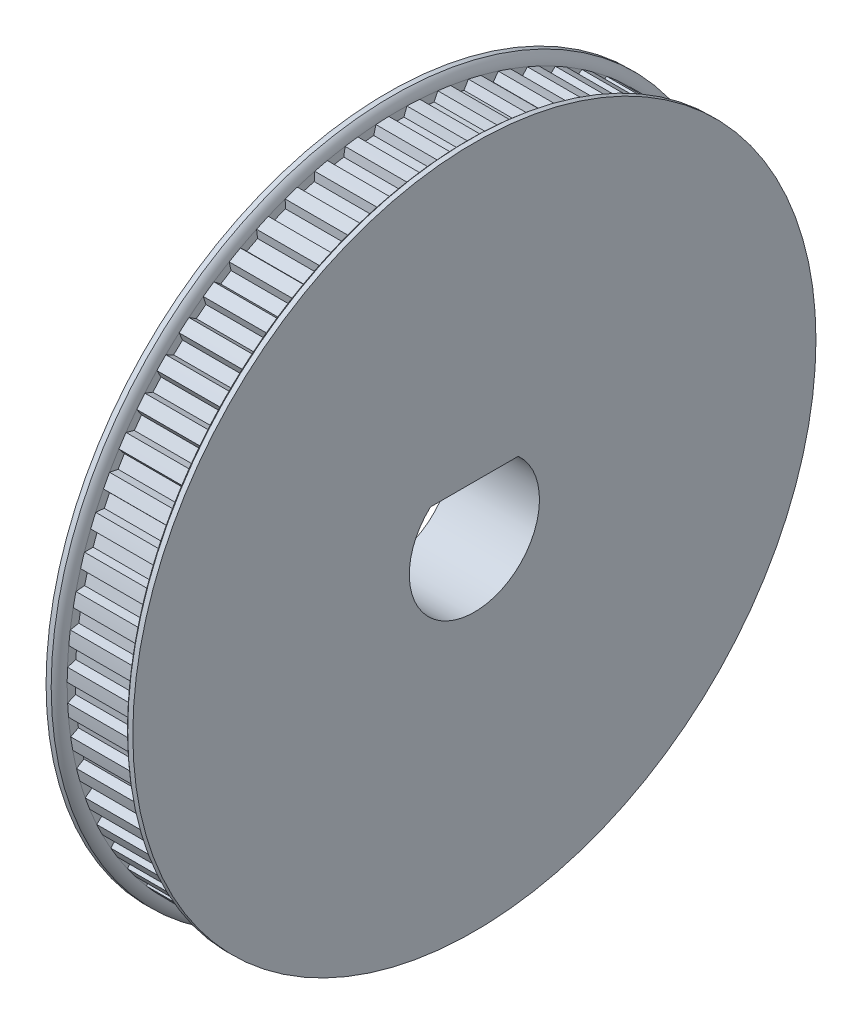
SolidWorks part; units mm, degrees
ref_plane "Front Plane" through (0, 0, 0) normal (0, 0, 1) x (1, 0, 0)
ref_plane "Top Plane" through (0, 0, 0) normal (0, 1, 0) x (1, 0, 0)
ref_plane "Right Plane" through (0, 0, 0) normal (1, 0, 0) x (0, 0, -1)
sketch "Sketch1" plane through (0, 0, 0) normal (1, 0, 0) x (0, 0, -1)
  line L3 (0, 0) -> (0, 51.2) construction
  line L6 (0, 51.2) -> (0, 52.4) construction
  line L7 (-1.325, 52.3832) -> (-0.8915, 51.1922)
  line L8 (1.325, 52.3832) -> (0.8915, 51.1922)
  line L9 (0, -2.2) -> (0, -3.2) construction
  line L10 (0, 52.9) -> (0, 52.4) construction
  line L12 (-0.8915, 51.1922) -> (0.8915, 51.1922)
  line L15 (0, 0) -> (0, -2.2) construction
  circle A0 centre (0, 0) radius 52.9 construction
  circle A1 centre (0, 0) radius 51.2 construction
  arc A7 (1.325, 52.3832) -> (-1.325, 52.3832) centre (0, 0) ccw
  dimension "PD" = 105.8
  dimension "D1" = 40
  dimension "D3" = 0.5
  dimension "D2" = 1.2
  dimension "D4" = 2.65
sketch "Sketch2" plane through (0, 0, 0) normal (0, 0, 1) x (1, 0, 0)
  line L0 (-10.5, 0) -> (10.5, 0) construction
  line L1 (-10.5, 4) -> (10.5, 4) construction
  line L2 (-10.5, 4) -> (-10.5, 19) construction
  line L3 (-2.2, 54) -> (-1.45, 54)
  line L4 (-0.7, 52.4) -> (-2.2, 52.4) construction
  line L5 (9.75, 52.4) -> (9.75, 54) construction
  line L6 (-0.7, 52.4) -> (9, 52.4)
  line L7 (-2.2, 19) -> (-2.2, 4)
  line L8 (9, 52.4) -> (10.5, 52.4) construction
  line L9 (9.75, 54) -> (10.5, 54)
  line L10 (10.5, 54) -> (10.5, 4)
  line L11 (-2.2, 4) -> (10.5, 4)
  line L12 (-6.35, 19) -> (-6.35, 4) construction
  line L13 (-2.2, 54) -> (-2.2, 19)
  line L14 (-2.2, 19) -> (-10.5, 19) construction
  arc A0 (9, 52.4) -> (9.75, 54) centre (11.0817, 52.4) cw
  arc A1 (-0.7, 52.4) -> (-1.45, 54) centre (-2.7817, 52.4) ccw
  point P19 (-0.7, 52.4)
  point P20 (9, 52.4)
  dimension "Bore Size" = 4
  dimension "Overall Width" = 21
  dimension "Inside Width" = 9.7
  dimension "Outside Width" = 12.7
  dimension "Hub Dia" = 19
  dimension "OD" = 108
sketch "Sketch6" plane through (0, 0, 0) normal (0, 0, 1) x (1, 0, 0)
  line L0 (9.75, 54) -> (10.5, 54) construction
  line L1 (-0.7, 52.4) -> (9, 52.4) construction
  line L2 (-2.2, 54) -> (-1.45, 54) construction
  line L3 (-2.2, 54) -> (-2.2, 19) construction
  line L4 (-2.2, 19) -> (-10.5, 19) construction
  line L5 (-10.5, 4) -> (-10.5, 19) construction
  line L6 (-10.5, 4) -> (10.5, 4) construction
  line L7 (10.5, 54) -> (10.5, 4) construction
  line L8 (9.75, 54) -> (10.5, 54)
  line L9 (-0.7, 52.4) -> (9, 52.4)
  line L10 (-2.2, 54) -> (-1.45, 54)
  line L11 (-2.2, 54) -> (-2.2, 19)
  line L12 (-2.2, 19) -> (-10.5, 19)
  line L13 (-10.5, 4) -> (-10.5, 19)
  line L14 (-10.5, 4) -> (10.5, 4)
  line L15 (10.5, 54) -> (10.5, 4)
  line L16 (-2.2, 19) -> (-2.2, 4)
  arc A0 (9.75, 54) -> (9, 52.4) centre (11.0817, 52.4) ccw construction
  arc A1 (-0.7, 52.4) -> (-1.45, 54) centre (-2.7817, 52.4) ccw construction
  arc A2 (9.75, 54) -> (9, 52.4) centre (11.0817, 52.4) ccw
  arc A3 (-0.7, 52.4) -> (-1.45, 54) centre (-2.7817, 52.4) ccw
revolve "Revolve1" add sketch "Sketch6" angle 360 about L14 region at (4.15, 28.3639, 0) other way angle 360
sketch "Sketch3" plane through (0, 0, 0) normal (1, 0, 0) x (0, 0, -1)
  line L2 (-1.325, 52.3832) -> (-0.8915, 51.1922) construction
  line L3 (-0.8915, 51.1922) -> (0.8915, 51.1922) construction
  line L4 (1.325, 52.3832) -> (0.8915, 51.1922) construction
  line L5 (-1.325, 52.3832) -> (-0.8915, 51.1922)
  line L6 (-0.8915, 51.1922) -> (0.8915, 51.1922)
  line L7 (1.325, 52.3832) -> (0.8915, 51.1922)
  arc A1 (1.325, 52.3832) -> (-1.325, 52.3832) centre (0, 0) ccw construction
  arc A2 (1.325, 52.3832) -> (-1.325, 52.3832) centre (0, 0) ccw
extrude "Cut-Extrude1" cut sketch "Sketch3" along normal up to vertex (9 mm away) from vertex up to point (9, 52.4, 0) starting at point (-0.7, 52.4, 0)
pattern_circular "CirPattern1" count 67 over 360 about axis through (-10.5, 4, 0) along (-1, 0, 0) of "Cut-Extrude1"
sketch "Sketch5" plane through (0, 0, 0) normal (0, 0, 1) x (1, 0, 0)
  line L0 (-10.5, 0) -> (10.5, 0) construction
  point P0 (9, 0)
sketch "Sketch8" plane through (-2.2, 0, 0) normal (-1, 0, 0) x (0, 0, 1)
  line L0 (-6.4323, 11.025) -> (6.4323, 11.025)
  arc A0 (-6.4323, 11.025) -> (6.4323, 11.025) centre (0, 4) ccw
  circle A1 centre (0, 4) radius 50 construction
  dimension "D1" = 19.05
  dimension "D2" = 7.025
extrude "Cut-Extrude2" cut sketch "Sketch8" against normal through all
equation "\"D3@Sketch1\" = \"ht@Sketch1\" / 2"
equation "\"D2@Sketch1\" = \"hs@Sketch1\" - \"ht@Sketch1\""
